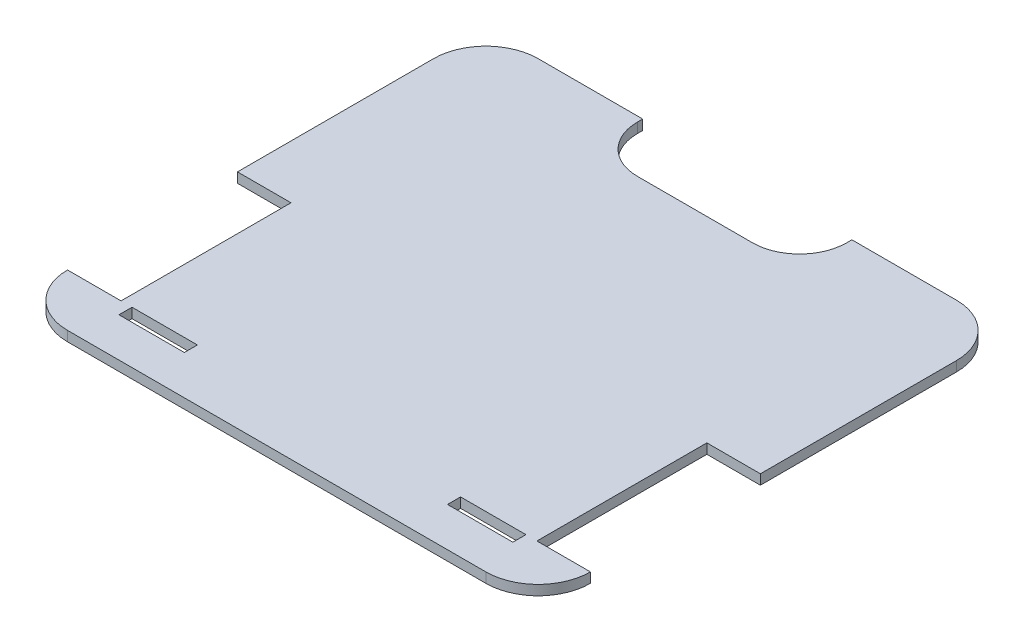
SolidWorks part; units mm, degrees
ref_plane "Front Plane" through (0, 0, 0) normal (0, 0, 1) x (1, 0, 0)
ref_plane "Top Plane" through (0, 0, 0) normal (0, 1, 0) x (1, 0, 0)
ref_plane "Right Plane" through (0, 0, 0) normal (1, 0, 0) x (0, 0, -1)
sketch "Sketch1" plane through (0, 0, 0) normal (0, 1, 0) x (1, 0, 0)
  line L1 (-127, 114.3) -> (127, 114.3)
  line L2 (-127, 114.3) -> (-127, -114.3)
  line L3 (-127, -114.3) -> (127, -114.3)
  line L4 (127, 114.3) -> (127, -114.3)
  line L5 (-127, 114.3) -> (127, -114.3) construction
  line L6 (-127, -114.3) -> (127, 114.3) construction
  point P0 (0, 0)
  dimension "D1" = 254
  dimension "D2" = 228.6
extrude "Boss-Extrude1" add sketch "Sketch1" along normal blind 4.826
sketch "Sketch2" plane through (0, 4.826, 0) normal (0, 1, 0) x (1, 0, 0)
  line L0 (-127, 114.3) -> (-127, -114.3) construction
  line L1 (-127, -6.35) -> (-101, -6.35)
  line L2 (-127, -6.35) -> (-127, -88.9)
  line L3 (-127, -88.9) -> (-101, -88.9)
  line L4 (-101, -6.35) -> (-101, -88.9)
  line L5 (127, -114.3) -> (127, 114.3) construction
  line L6 (127, -6.35) -> (101, -6.35)
  line L7 (127, -6.35) -> (127, -88.9)
  line L8 (127, -88.9) -> (101, -88.9)
  line L9 (101, -6.35) -> (101, -88.9)
  line L10 (-127, -114.3) -> (127, -114.3) construction
  dimension "D1" = 25.4
  dimension "D2" = 25.4
  dimension "D3" = 82.55
  dimension "D4" = 82.55
  dimension "D5" = 26
  dimension "D6" = 26
extrude "Cut-Extrude1" cut sketch "Sketch2" against normal blind 4.826
sketch "Sketch4" plane through (0, 4.826, 0) normal (0, 1, 0) x (1, 0, 0)
  line L0 (0, -114.3) -> (0, 114.3) construction
  line L1 (-127, -114.3) -> (127, -114.3) construction
  line L2 (127, 114.3) -> (-127, 114.3) construction
  line L3 (-127, 88.9) -> (-101.6, 88.9) construction
  line L4 (-127, 114.3) -> (-127, -6.35) construction
  line L5 (-101.6, 88.9) -> (-101.6, 114.3) construction
  line L6 (-127, 88.9) -> (-127, 114.3)
  line L7 (-127, 114.3) -> (-101.6, 114.3)
  line L8 (127, 88.9) -> (127, 114.3)
  line L9 (127, 114.3) -> (101.6, 114.3)
  arc A0 (-127, 88.9) -> (-101.6, 114.3) centre (-101.6, 88.9) cw
  arc A1 (127, 88.9) -> (101.6, 114.3) centre (101.6, 88.9) ccw
extrude "Cut-Extrude3" cut sketch "Sketch4" against normal blind 4.826
sketch "Sketch7" plane through (0, 4.826, 0) normal (0, 1, 0) x (1, 0, 0)
  line L0 (0, -114.3) -> (0, 114.3) construction
  line L1 (-127, -114.3) -> (127, -114.3) construction
  line L2 (101.6, 114.3) -> (-101.6, 114.3) construction
  line L3 (50.8, 88.9) -> (50.8, 114.3)
  line L4 (50.8, 88.9) -> (-50.8, 88.9)
  line L5 (0, 88.9) -> (0, 114.3)
  line L6 (50.8, 114.3) -> (-50.8, 114.3)
  line L7 (-50.8, 88.9) -> (-50.8, 114.3)
  line M6 (101.6, 114.3) -> (-101.6, 114.3)
  dimension "D2" = 50.8
extrude "Cut-Extrude5" cut sketch "Sketch7" against normal blind 4.826 contours L7 L4 L5 M6 | L5 L4 L3 M6 region at (25.4, 4.826, -101.6) region at (-25.4, 4.826, -101.6)
fillet "Fillet9" radius 22.86 1 edges at (-50.8, 2.413, -88.9) type face fillet first side face at (0, 2.413, -88.9) second side face at (-50.8, 2.413, -101.6)
fillet "Fillet10" radius 22.86 1 edges at (50.8, 2.413, -88.9) type face fillet first side face at (11.43, 2.413, -88.9) second side face at (50.8, 2.413, -101.6)
sketch "Sketch8" plane through (0, 4.826, 0) normal (0, 1, 0) x (1, 0, 0)
  line L0 (-127, -88.9) -> (-101.6, -88.9) construction
  line L1 (-101.6, -88.9) -> (-101.6, -114.3) construction
  line L2 (-127, -114.3) -> (127, -114.3) construction
  line L3 (-127, -88.9) -> (-127, -114.3)
  line L4 (-127, -114.3) -> (-101.6, -114.3)
  line L5 (0, -114.3) -> (0, 88.9) construction
  line L6 (27.94, 88.9) -> (-27.94, 88.9) construction
  line L7 (127, -114.3) -> (101.6, -114.3)
  line L8 (127, -88.9) -> (127, -114.3)
  arc A0 (-127, -88.9) -> (-101.6, -114.3) centre (-101.6, -88.9) ccw
  arc A1 (127, -88.9) -> (101.6, -114.3) centre (101.6, -88.9) cw
extrude "Cut-Extrude6" cut sketch "Sketch8" against normal blind 4.826
sketch "Sketch9" plane through (0, 0, 0) normal (0, -1, 0) x (1, 0, 0)
  line L0 (-58.582, 88.9) -> (-101, 88.9) construction
  line L1 (-95.666, 88.9) -> (-63.916, 88.9)
  line L2 (-95.666, 88.9) -> (-95.666, 95.25)
  line L3 (-95.666, 95.25) -> (-63.916, 95.25)
  line L4 (-63.916, 88.9) -> (-63.916, 95.25)
  line L5 (-101, 88.9) -> (-95.666, 88.9) construction
  line L6 (-63.916, 88.9) -> (-58.582, 88.9) construction
  line L7 (0, 114.3) -> (0, -88.9) construction
  line L8 (-101.6, 114.3) -> (101.6, 114.3) construction
  line L9 (27.94, -88.9) -> (-27.94, -88.9) construction
  line L10 (63.916, 88.9) -> (58.582, 88.9) construction
  line L11 (101, 88.9) -> (95.666, 88.9) construction
  line L12 (63.916, 88.9) -> (63.916, 95.25)
  line L13 (95.666, 95.25) -> (63.916, 95.25)
  line L14 (95.666, 88.9) -> (95.666, 95.25)
  line L15 (95.666, 88.9) -> (63.916, 88.9)
  dimension "D1" = 31.75
  dimension "D2" = 6.35
extrude "Cut-Extrude7" cut sketch "Sketch9" against normal through all
equation "\"MDF\"= 0.19in"
equation "\"GenDiameter\"= 60mm"
equation "\"GenCutDiameter\" = 1.8in"
equation "\"GenCutDistance\" = 1"
equation "\"TowerHeight\" = 6in"
equation "\"TowerFrontBase\" = 3in"
equation "\"FunnelHeight\" = 1in"
equation "\"FunnelAngle\" = 20"
equation "\"TowerSideBase\" = 3in"
equation "\"BaseLength\" = 9in"
equation "\"BaseWidth\" = 10in"
equation "\"WheelHoleLength\" = 3.25in"
equation "\"WheelHoleWidth\" = 26mm"
equation "\"DropLength\" = 1in"
equation "\"D1@Sketch1\"=\"BaseWidth\""
equation "\"D2@Sketch1\"=\"BaseLength\""
equation "\"D1@Boss-Extrude1\"=\"MDF\""
equation "\"WheelHoleFromBack\" = 1in"
equation "\"D1@Sketch2\"=\"WheelHoleFromBack\""
equation "\"D2@Sketch2\"=\"WheelHoleFromBack\""
equation "\"D3@Sketch2\"=\"WheelHoleLength\""
equation "\"D4@Sketch2\"=\"WheelHoleLength\""
equation "\"D5@Sketch2\"=\"WheelHoleWidth\""
equation "\"D6@Sketch2\"=\"WheelHoleWidth\""
equation "\"D1@Cut-Extrude1\"=\"MDF\""
equation "\"DropWidth\" = 8.5in"
equation "\"BumperWidth\" = 1in"
equation "\"D1@Sketch4\"=\"BumperWidth\""
equation "\"D2@Sketch4\"=\"WheelHoleFromBack\""
equation "\"D1@Cut-Extrude3\"=\"MDF\""
equation "\"D1@Sketch7\"=\"DropLength\""
equation "\"D2@Sketch7\"=\"DropWidthTop\"/2"
equation "\"D1@Cut-Extrude5\"=\"MDF\""
equation "\"D1@Sketch8\"=\"BumperWidth\""
equation "\"D1@Cut-Extrude6\"=\"MDF\""
equation "\"DropWidthTop\" = 4in"
